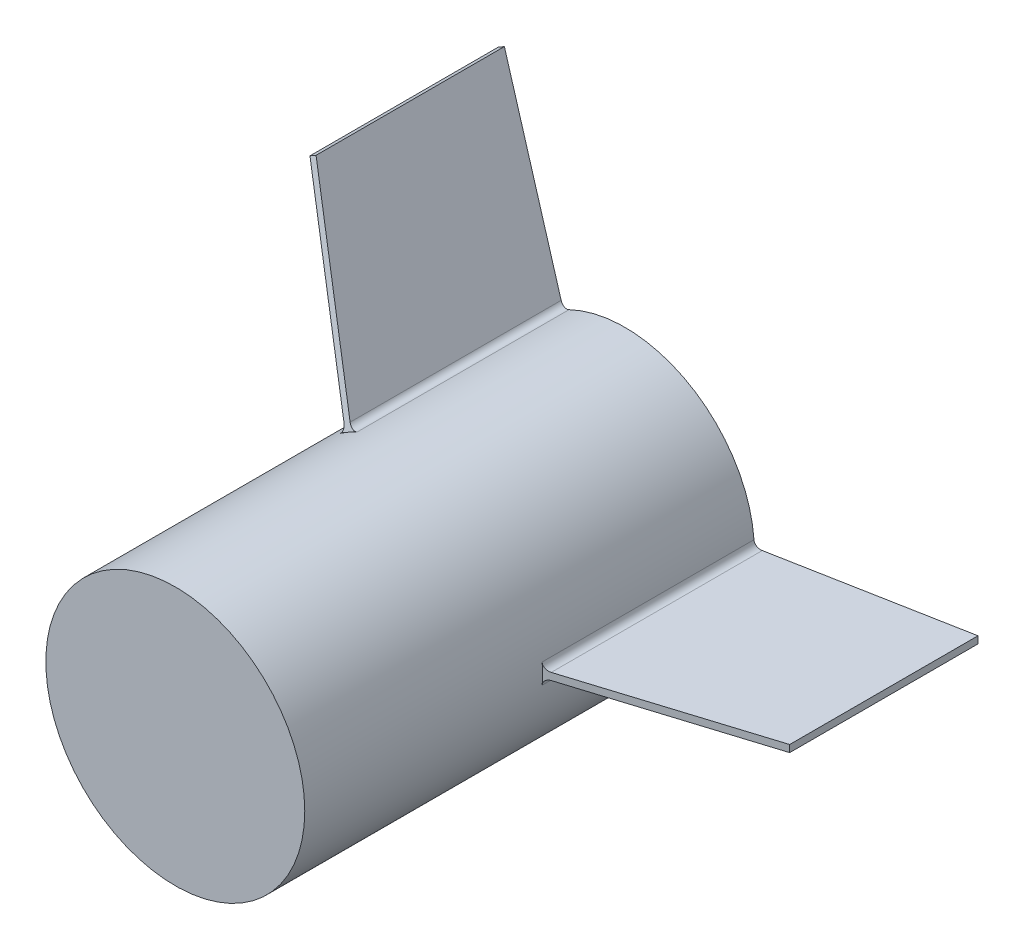
SolidWorks part; units mm, degrees
ref_plane "前视基准面" through (0, 0, 0) normal (0, 0, 1) x (1, 0, 0)
ref_plane "上视基准面" through (0, 0, 0) normal (0, 1, 0) x (1, 0, 0)
ref_plane "右视基准面" through (0, 0, 0) normal (1, 0, 0) x (0, 0, -1)
other "Configuration Table"
sketch "草图1" plane through (0, 0, 0) normal (0, 0, 1) x (1, 0, 0)
  circle A1 centre (0, 0) radius 55
  dimension "D1" = 110
extrude "凸台-拉伸1" add sketch "草图1" along normal blind 190
sketch "草图2" plane through (0, 0, 190) normal (0, 0, 1) x (1, 0, 0)
  circle A0 centre (0, 0) radius 53
  dimension "D1" = 106
extrude "切除-拉伸1" cut sketch "草图2" against normal blind 188
sketch "草图3" plane through (0, 0, 0) normal (0, 0, -1) x (-1, 0, 0)
  circle A0 centre (0, 0) radius 15
  dimension "D1" = 30
extrude "切除-拉伸2" cut sketch "草图3" against normal blind 10
sketch "草图4" plane through (0, 0, 2) normal (0, 0, 1) x (1, 0, 0)
  circle A0 centre (0, 0) radius 15
  circle A1 centre (0, 0) radius 16
  dimension "D1" = 32
extrude "凸台-拉伸2" add sketch "草图4" along normal blind 188
sketch "草图5" plane through (0, 0, 190) normal (0, 0, 1) x (1, 0, 0)
  circle A0 centre (0, 0) radius 55
extrude "凸台-拉伸5" add sketch "草图5" along normal blind 1
sketch "草图6" plane through (0, 0, 191) normal (0, 0, 1) x (1, 0, 0)
  line L0 (0, 0) -> (-55, 0)
  line L1 (0, 0) -> (27.5, 47.6314)
  line L2 (0, 0) -> (27.5, -47.6314)
  circle A0 centre (0, 0) radius 55 construction
  point P10 (0, 0)
  dimension "D1" = 3
ref_plane "基准面1" through (0, 0, 0) normal (0, 1, 0) x (-1, 0, 0)
sketch "草图8" plane through (0, 0, 0) normal (0, 1, 0) x (-1, 0, 0)
  line L0 (-55, 90) -> (-135, 65)
  line L1 (-55, 191) -> (-55, 0) construction
  line L2 (-135, 65) -> (-135, -15)
  line L3 (-135, -15) -> (-55, 0)
  line L5 (-55, 90) -> (-53, 90)
  line L6 (-53, 90) -> (-53, 0)
  line L7 (-55, 0) -> (55, 0) construction
  line L8 (-53, 0) -> (-55, 0)
  dimension "D1" = 65
  dimension "D2" = 25
  dimension "D3" = 80
  dimension "D4" = 2
  dimension "D5" = 80
extrude "凸台-拉伸6" add sketch "草图8" along normal mid plane 3
pattern_circular "阵列(圆周)1" count 3 over 360 about axis through (0, 0, 190) along (0, 0, -1) of "凸台-拉伸6"
fillet "圆角1" radius 3 6 edges at (-28.7888, -46.8637, 45) (-26.1907, -48.3637, 45) (54.9795, -1.5, 45) (54.9795, 1.5, 45) (-26.1907, 48.3637, 45) (-28.7888, 46.8637, 45)
